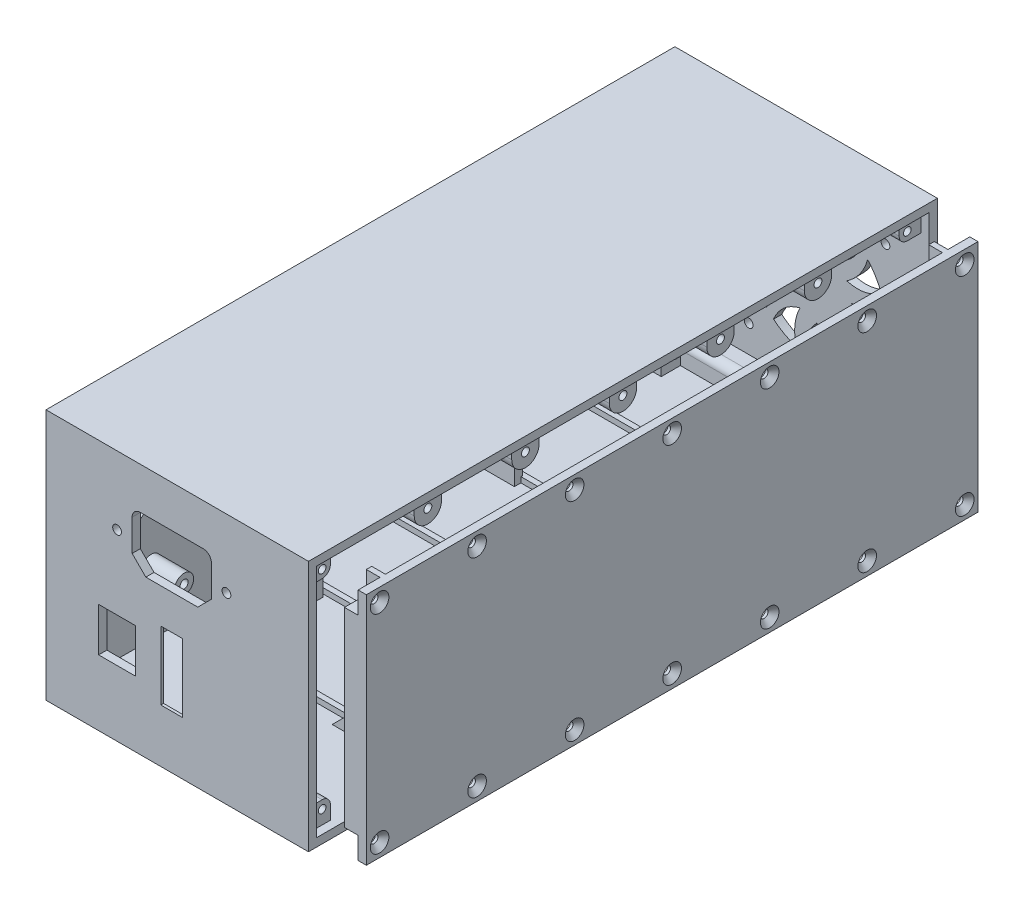
SolidWorks part; units mm, degrees
ref_plane "Front Plane" through (0, 0, 0) normal (0, 0, 1) x (1, 0, 0)
ref_plane "Top Plane" through (0, 0, 0) normal (0, 1, 0) x (1, 0, 0)
ref_plane "Right Plane" through (0, 0, 0) normal (1, 0, 0) x (0, 0, -1)
sketch "Sketch1" plane through (0, 0, 0) normal (1, 0, 0) x (0, 0, -1)
  line L1 (115, 46) -> (-115, 46)
  line L2 (115, 46) -> (115, -46)
  line L3 (115, -46) -> (-115, -46)
  line L4 (-115, 46) -> (-115, -46)
  line L5 (115, 46) -> (-115, -46) construction
  line L6 (115, -46) -> (-115, 46) construction
  point P0 (0, 0)
  dimension "D1" = 92
  dimension "D2" = 230
extrude "Boss-Extrude1" add sketch "Sketch1" along normal blind 3
sketch "Sketch2" plane through (3, 0, 0) normal (1, 0, 0) x (0, 0, -1)
  line L0 (-112, 43) -> (-112, -43)
  line L1 (-112, -43) -> (112, -43)
  line L2 (112, -43) -> (112, 43)
  line L3 (112, 43) -> (-112, 43)
  line L4 (-115, 46) -> (-115, -46)
  line L5 (-115, -46) -> (115, -46)
  line L6 (115, -46) -> (115, 46)
  line L7 (115, 46) -> (-115, 46)
  line L8 (-115, 46) -> (-115, -46)
  line L9 (-115, -46) -> (115, -46)
  line L10 (115, -46) -> (115, 46)
  line L11 (115, 46) -> (-115, 46)
  dimension "D1" = 0
  dimension "D2" = 3
extrude "Boss-Extrude2" add sketch "Sketch2" along normal blind 93
sketch "Sketch3" plane through (0, 0, 0) normal (-1, 0, 0) x (0, 0, 1)
  line L0 (-115, 0) -> (115, 0) construction
  line L1 (-115, -46) -> (-115, 46) construction
  line L2 (115, 46) -> (115, -46) construction
  line L3 (0, 46) -> (0, -46) construction
  line L4 (-115, 46) -> (115, 46) construction
  line L5 (115, -46) -> (-115, -46) construction
  line L6 (26.5, -7.75) -> (18.5, -7.75)
  line L7 (11.5, 7.75) -> (3.5, 7.75)
  line L8 (11.5, 7.75) -> (11.5, -7.75)
  line L9 (11.5, -7.75) -> (3.5, -7.75)
  line L10 (3.5, 7.75) -> (3.5, -7.75)
  line L11 (11.5, 7.75) -> (3.5, -7.75) construction
  line L12 (11.5, -7.75) -> (3.5, 7.75) construction
  line L13 (26.5, 7.75) -> (26.5, -7.75)
  line L14 (26.5, 7.75) -> (18.5, 7.75)
  line L15 (18.5, 7.75) -> (18.5, -7.75)
  line L16 (41.5, -7.75) -> (33.5, -7.75)
  line L17 (41.5, 7.75) -> (41.5, -7.75)
  line L18 (41.5, 7.75) -> (33.5, 7.75)
  line L19 (33.5, 7.75) -> (33.5, -7.75)
  line L20 (56.5, -7.75) -> (48.5, -7.75)
  line L21 (56.5, 7.75) -> (56.5, -7.75)
  line L22 (56.5, 7.75) -> (48.5, 7.75)
  line L23 (48.5, 7.75) -> (48.5, -7.75)
  line L24 (71.5, -7.75) -> (63.5, -7.75)
  line L25 (71.5, 7.75) -> (71.5, -7.75)
  line L26 (71.5, 7.75) -> (63.5, 7.75)
  line L27 (63.5, 7.75) -> (63.5, -7.75)
  line L28 (11.5, -7.75) -> (3.5, -7.75)
  line L29 (11.5, 7.75) -> (11.5, -7.75)
  line L30 (11.5, 7.75) -> (3.5, 7.75)
  line L31 (3.5, 7.75) -> (3.5, -7.75)
  line L32 (26.5, -7.75) -> (18.5, -7.75)
  line L33 (26.5, 7.75) -> (26.5, -7.75)
  line L34 (26.5, 7.75) -> (18.5, 7.75)
  line L35 (18.5, 7.75) -> (18.5, -7.75)
  line L36 (41.5, -7.75) -> (33.5, -7.75)
  line L37 (41.5, 7.75) -> (41.5, -7.75)
  line L38 (41.5, 7.75) -> (33.5, 7.75)
  line L39 (33.5, 7.75) -> (33.5, -7.75)
  line L40 (56.5, -7.75) -> (48.5, -7.75)
  line L41 (56.5, 7.75) -> (56.5, -7.75)
  line L42 (56.5, 7.75) -> (48.5, 7.75)
  line L43 (48.5, 7.75) -> (48.5, -7.75)
  line L44 (-3.5, -7.75) -> (-11.5, -7.75)
  line L45 (-3.5, 7.75) -> (-3.5, -7.75)
  line L46 (-3.5, 7.75) -> (-11.5, 7.75)
  line L47 (-11.5, 7.75) -> (-11.5, -7.75)
  line L48 (11.5, -7.75) -> (3.5, -7.75)
  line L49 (11.5, 7.75) -> (11.5, -7.75)
  line L50 (11.5, 7.75) -> (3.5, 7.75)
  line L51 (3.5, 7.75) -> (3.5, -7.75)
  line L52 (26.5, -7.75) -> (18.5, -7.75)
  line L53 (26.5, 7.75) -> (26.5, -7.75)
  line L54 (26.5, 7.75) -> (18.5, 7.75)
  line L55 (18.5, 7.75) -> (18.5, -7.75)
  line L56 (41.5, -7.75) -> (33.5, -7.75)
  line L57 (41.5, 7.75) -> (41.5, -7.75)
  line L58 (41.5, 7.75) -> (33.5, 7.75)
  line L59 (33.5, 7.75) -> (33.5, -7.75)
  line L60 (-18.5, -7.75) -> (-26.5, -7.75)
  line L61 (-18.5, 7.75) -> (-18.5, -7.75)
  line L62 (-18.5, 7.75) -> (-26.5, 7.75)
  line L63 (-26.5, 7.75) -> (-26.5, -7.75)
  line L64 (-3.5, -7.75) -> (-11.5, -7.75)
  line L65 (-3.5, 7.75) -> (-3.5, -7.75)
  line L66 (-3.5, 7.75) -> (-11.5, 7.75)
  line L67 (-11.5, 7.75) -> (-11.5, -7.75)
  line L68 (11.5, -7.75) -> (3.5, -7.75)
  line L69 (11.5, 7.75) -> (11.5, -7.75)
  line L70 (11.5, 7.75) -> (3.5, 7.75)
  line L71 (3.5, 7.75) -> (3.5, -7.75)
  line L72 (26.5, -7.75) -> (18.5, -7.75)
  line L73 (26.5, 7.75) -> (26.5, -7.75)
  line L74 (26.5, 7.75) -> (18.5, 7.75)
  line L75 (18.5, 7.75) -> (18.5, -7.75)
  line L76 (-33.5, -7.75) -> (-41.5, -7.75)
  line L77 (-33.5, 7.75) -> (-33.5, -7.75)
  line L78 (-33.5, 7.75) -> (-41.5, 7.75)
  line L79 (-41.5, 7.75) -> (-41.5, -7.75)
  line L80 (-18.5, -7.75) -> (-26.5, -7.75)
  line L81 (-18.5, 7.75) -> (-18.5, -7.75)
  line L82 (-18.5, 7.75) -> (-26.5, 7.75)
  line L83 (-26.5, 7.75) -> (-26.5, -7.75)
  line L84 (-3.5, -7.75) -> (-11.5, -7.75)
  line L85 (-3.5, 7.75) -> (-3.5, -7.75)
  line L86 (-3.5, 7.75) -> (-11.5, 7.75)
  line L87 (-11.5, 7.75) -> (-11.5, -7.75)
  line L88 (11.5, -7.75) -> (3.5, -7.75)
  line L89 (11.5, 7.75) -> (11.5, -7.75)
  line L90 (11.5, 7.75) -> (3.5, 7.75)
  line L91 (3.5, 7.75) -> (3.5, -7.75)
  line L92 (-48.5, -7.75) -> (-56.5, -7.75)
  line L93 (-48.5, 7.75) -> (-48.5, -7.75)
  line L94 (-48.5, 7.75) -> (-56.5, 7.75)
  line L95 (-56.5, 7.75) -> (-56.5, -7.75)
  line L96 (-33.5, -7.75) -> (-41.5, -7.75)
  line L97 (-33.5, 7.75) -> (-33.5, -7.75)
  line L98 (-33.5, 7.75) -> (-41.5, 7.75)
  line L99 (-41.5, 7.75) -> (-41.5, -7.75)
  line L100 (-18.5, -7.75) -> (-26.5, -7.75)
  line L101 (-18.5, 7.75) -> (-18.5, -7.75)
  line L102 (-18.5, 7.75) -> (-26.5, 7.75)
  line L103 (-26.5, 7.75) -> (-26.5, -7.75)
  line L104 (-3.5, -7.75) -> (-11.5, -7.75)
  line L105 (-3.5, 7.75) -> (-3.5, -7.75)
  line L106 (-3.5, 7.75) -> (-11.5, 7.75)
  line L107 (-11.5, 7.75) -> (-11.5, -7.75)
  line L108 (-3.5, -7.75) -> (-11.5, -7.75)
  line L109 (-3.5, 7.75) -> (-3.5, -7.75)
  line L110 (-3.5, 7.75) -> (-11.5, 7.75)
  line L111 (-11.5, 7.75) -> (-11.5, -7.75)
  line L112 (-18.5, -7.75) -> (-26.5, -7.75)
  line L113 (-18.5, 7.75) -> (-18.5, -7.75)
  line L114 (-18.5, 7.75) -> (-26.5, 7.75)
  line L115 (-26.5, 7.75) -> (-26.5, -7.75)
  line L116 (-33.5, -7.75) -> (-41.5, -7.75)
  line L117 (-33.5, 7.75) -> (-33.5, -7.75)
  line L118 (-33.5, 7.75) -> (-41.5, 7.75)
  line L119 (-41.5, 7.75) -> (-41.5, -7.75)
  line L120 (-48.5, -7.75) -> (-56.5, -7.75)
  line L121 (-48.5, 7.75) -> (-48.5, -7.75)
  line L122 (-48.5, 7.75) -> (-56.5, 7.75)
  line L123 (-56.5, 7.75) -> (-56.5, -7.75)
  line L124 (-63.5, -7.75) -> (-71.5, -7.75)
  line L125 (-63.5, 7.75) -> (-63.5, -7.75)
  line L126 (-63.5, 7.75) -> (-71.5, 7.75)
  line L127 (-71.5, 7.75) -> (-71.5, -7.75)
  circle A0 centre (84.6037, 0) radius 1
  point P12 (7.5, 0)
  dimension "D6" = 2
  dimension "D1" = 7.5
  dimension "D2" = 15.5
  dimension "D3" = 8
  dimension "D4" = 5
  dimension "D5" = 6
extrude "Cut-Extrude1" cut sketch "Sketch3" against normal up to surface (3 mm away) contours L126 L127 L124 L125 | L94 L95 L92 L93 | L78 L79 L76 L77 | L62 L63 L60 L61 | L46 L47 L44 L45 | L7 L10 L9 L8 | L14 L15 L6 L13 | L18 L19 L16 L17 | L22 L23 L20 L21 | L26 L27 L24 L25 | A0 region at (0, 0, 22.5) region at (0, 0, 7.5) region at (0, 0, 37.5) region at (0, 0, 52.5) region at (0, 0, 67.5) region at (0, 0, -7.5) region at (0, 0, -22.5) region at (0, 0, -37.5) region at (0, 0, -52.5) region at (0, 0, -67.5) region at (0, 0, 84.6037) up to face at (3, 0, 0)
sketch "Sketch4" plane through (96, 0, 0) normal (1, 0, 0) x (0, 0, -1)
  line L0 (0, 43) -> (0, -43) construction
  line L1 (112, 43) -> (-112, 43) construction
  line L2 (-112, -43) -> (112, -43) construction
  line L3 (-112, 43) -> (-112, -43) construction
  line L4 (-104, 38) -> (-104, 43)
  line L5 (-104, 43) -> (-112, 43)
  line L6 (-112, 43) -> (-112, 35)
  line L7 (-112, 35) -> (-107, 35)
  line L8 (0, 0) -> (-112, 0) construction
  line L9 (-107, -35) -> (-112, -35)
  line L10 (-112, 43) -> (-112, -43) construction
  line L11 (-112, -35) -> (-112, -43)
  line L12 (-104, -38) -> (-104, -43)
  line L13 (-104, -43) -> (-112, -43)
  line L14 (104, -43) -> (112, -43)
  line L15 (112, -35) -> (112, -43)
  line L16 (107, -35) -> (112, -35)
  line L17 (112, 35) -> (107, 35)
  line L18 (112, 43) -> (112, 35)
  line L19 (104, 43) -> (112, 43)
  line L20 (104, 38) -> (104, 43)
  line L21 (104, -38) -> (104, -43)
  circle A0 centre (-107, 38) radius 1.4
  circle A1 centre (-107, -38) radius 1.4
  arc A2 (-104, 38) -> (-107, 35) centre (-107, 38) cw
  arc A3 (-107, -35) -> (-104, -38) centre (-107, -38) cw
  arc A4 (107, -35) -> (104, -38) centre (107, -38) ccw
  circle A5 centre (107, -38) radius 1.4
  arc A6 (104, 38) -> (107, 35) centre (107, 38) ccw
  circle A7 centre (107, 38) radius 1.4
  dimension "D5" = 2.8
  dimension "D6" = 3
  dimension "D1" = 5
  dimension "D2" = 5
  dimension "D3" = 5
  dimension "D4" = 5
extrude "Boss-Extrude3" add sketch "Sketch4" against normal up to surface (93 mm away) from offset 3 up to face at (3, 0, -67.5) offset against normal yes
sketch "Sketch5" plane through (93, 0, 0) normal (1, 0, 0) x (0, 0, -1)
  circle A0 centre (-107, -38) radius 1.4 construction
  circle A1 centre (107, -38) radius 1.4 construction
  circle A2 centre (107, 38) radius 1.4 construction
  circle A3 centre (-107, 38) radius 1.4 construction
  circle A4 centre (-107, -38) radius 1.4
  circle A5 centre (107, -38) radius 1.4
  circle A6 centre (107, 38) radius 1.4
  circle A7 centre (-107, 38) radius 1.4
extrude "Boss-Extrude4" add sketch "Sketch5" against normal up to surface (90 mm away) from offset 20 up to face at (3, 0, -67.5) offset against normal yes
sketch "Sketch6" plane through (0, 0, 115) normal (0, 0, 1) x (1, 0, 0)
  line L0 (46, 46) -> (46, -46) construction
  line L1 (96, 46) -> (0, 46) construction
  line L2 (96, -46) -> (0, -46) construction
  line L3 (93, 43) -> (93, 38) construction
  line L4 (79.2275, 21) -> (12.7725, 21) construction
  line L5 (36.5, 11.25) -> (31.5, 16.25)
  line L6 (57.5, 30.75) -> (34.5, 30.75)
  line L7 (60.5, 27.75) -> (60.5, 16.25)
  line L8 (55.5, 11.25) -> (36.5, 11.25)
  line L9 (31.5, 27.75) -> (31.5, 16.25)
  line L10 (60.5, 30.75) -> (31.5, 11.25) construction
  line L11 (60.5, 11.25) -> (31.5, 30.75) construction
  line L12 (60.5, 16.25) -> (55.5, 11.25)
  line L14 (50, -1.5) -> (42, -1.5)
  line L15 (50, -1.5) -> (50, -26.5)
  line L16 (50, -26.5) -> (42, -26.5)
  line L17 (42, -1.5) -> (42, -26.5)
  line L18 (50, -1.5) -> (42, -26.5) construction
  line L19 (50, -26.5) -> (42, -1.5) construction
  line L20 (32.75, -6) -> (19.25, -6)
  line L21 (32.75, -6) -> (32.75, -22)
  line L22 (32.75, -22) -> (19.25, -22)
  line L23 (19.25, -6) -> (19.25, -22)
  line L24 (32.75, -6) -> (19.25, -22) construction
  line L25 (32.75, -22) -> (19.25, -6) construction
  circle A2 centre (26, 21) radius 1.6
  circle A3 centre (66, 21) radius 1.6
  arc A4 (57.5, 30.75) -> (60.5, 27.75) centre (57.5, 27.75) cw
  arc A5 (34.5, 30.75) -> (31.5, 27.75) centre (34.5, 27.75) ccw
  point P11 (46, 21)
  point P15 (46, 21)
  point P30 (46, -14)
  point P35 (26, -14)
  dimension "D2" = 3.2
  dimension "D7" = 3
  dimension "D1" = 47
  dimension "D3" = 20
  dimension "D4" = 20
  dimension "D5" = 29
  dimension "D6" = 19.5
  dimension "D8" = 25
  dimension "D9" = 8
  dimension "D10" = 25
  dimension "D13" = 32
  dimension "D14" = 20
  dimension "D15" = 13.5
  dimension "D16" = 16
extrude "Cut-Extrude2" cut sketch "Sketch6" against normal up to surface (3 mm away) up to face at (71.25, 0, 112)
sketch "Sketch7" plane through (0, 0, 112) normal (0, 0, -1) x (-1, 0, 0)
  line L0 (-39.5, 6) -> (-39.5, -32.5)
  line L1 (-39.5, -32.5) -> (-52, -32.5)
  line L2 (-52, -32.5) -> (-52, 6)
  line L3 (-52, 6) -> (-39.5, 6)
  line L4 (-50, -1.5) -> (-42, -1.5) construction
  line L5 (-50, -26.5) -> (-50, -1.5) construction
  dimension "D1" = 7.5
  dimension "D2" = 2
  dimension "D3" = 38.5
  dimension "D4" = 12.5
extrude "Cut-Extrude3" cut sketch "Sketch7" against normal blind 2
chamfer "Chamfer1" distance 2 angle 45 1 edges at (52, -13.25, 112)
sketch "Sketch8" plane through (3, 0, 0) normal (1, 0, 0) x (0, 0, -1)
  line L0 (-71.5, 0) -> (91.1958, 0) construction
  line L1 (-71.5, -7.75) -> (-71.5, 7.75) construction
  line L2 (-79.5, 43) -> (-79.5, -43) construction
  line L3 (112, 43) -> (-112, 43) construction
  line L4 (-104, -43) -> (104, -43) construction
  circle A0 centre (-79.5, 19.5) radius 1.5
  circle A1 centre (-79.5, -19.5) radius 1.5
  circle A2 centre (-79.5, 19.5) radius 3.5
  circle A3 centre (-79.5, -19.5) radius 3.5
  circle A4 centre (72, -19.5) radius 1.5
  circle A5 centre (72, -19.5) radius 3.5
  circle A6 centre (72, 19.5) radius 3.5
  circle A7 centre (72, 19.5) radius 1.5
  dimension "D1" = 3
  dimension "D2" = 7
  dimension "D3" = 8
  dimension "D5" = 19.5
  dimension "D6" = 19.5
  dimension "D7" = 19.5
  dimension "D8" = 19.5
  dimension "D9" = 151.5
extrude "Boss-Extrude5" add sketch "Sketch8" along normal blind 12
sketch "Sketch9" plane through (3, 0, 0) normal (1, 0, 0) x (0, 0, -1)
  circle A0 centre (-84.6037, 0) radius 3
extrude "Cut-Extrude4" cut sketch "Sketch9" against normal blind 2.2
ref_plane "Plane1" through (106, 0, 0) normal (1, 0, 0) x (0, 0, -1)
sketch "Sketch10" plane through (106, 0, 0) normal (1, 0, 0) x (0, 0, -1)
  line L112 (107, -32.85) -> (109.85, -32.85)
  line L113 (109.85, -32.85) -> (109.85, 32.85)
  line L114 (109.85, 32.85) -> (107, 32.85)
  line L115 (101.85, 38) -> (101.85, 40.85)
  line L116 (101.85, 40.85) -> (-101.85, 40.85)
  line L117 (-101.85, 40.85) -> (-101.85, 38)
  line L118 (-107, 32.85) -> (-109.85, 32.85)
  line L119 (-109.85, 32.85) -> (-109.85, -32.85)
  line L120 (-109.85, -32.85) -> (-107, -32.85)
  line L121 (-101.85, -38) -> (-101.85, -40.85)
  line L122 (-101.85, -40.85) -> (101.85, -40.85)
  line L123 (101.85, -40.85) -> (101.85, -38)
  line L124 (107, -34.85) -> (111.85, -34.85)
  line L125 (103.85, -42.85) -> (103.85, -38)
  line L126 (-103.85, -42.85) -> (103.85, -42.85)
  line L127 (-103.85, -38) -> (-103.85, -42.85)
  line L128 (-111.85, -34.85) -> (-107, -34.85)
  line L129 (-111.85, 34.85) -> (-111.85, -34.85)
  line L130 (-107, 34.85) -> (-111.85, 34.85)
  line L131 (-103.85, 42.85) -> (-103.85, 38)
  line L132 (103.85, 42.85) -> (-103.85, 42.85)
  line L133 (103.85, 38) -> (103.85, 42.85)
  line L134 (111.85, 34.85) -> (107, 34.85)
  line L135 (111.85, -34.85) -> (111.85, 34.85)
  line L136 (107, -34.85) -> (111.85, -34.85)
  line L137 (103.85, -42.85) -> (103.85, -38)
  line L138 (-103.85, -42.85) -> (103.85, -42.85)
  line L139 (-103.85, -38) -> (-103.85, -42.85)
  line L140 (-111.85, -34.85) -> (-107, -34.85)
  line L141 (-111.85, 34.85) -> (-111.85, -34.85)
  line L142 (-107, 34.85) -> (-111.85, 34.85)
  line L143 (-103.85, 42.85) -> (-103.85, 38)
  line L144 (103.85, 42.85) -> (-103.85, 42.85)
  line L145 (103.85, 38) -> (103.85, 42.85)
  line L146 (111.85, 34.85) -> (107, 34.85)
  line L147 (111.85, -34.85) -> (111.85, 34.85)
  arc A36 (107, -34.85) -> (103.85, -38) centre (107, -38) ccw
  arc A37 (-103.85, -38) -> (-107, -34.85) centre (-107, -38) ccw
  arc A38 (-107, 34.85) -> (-103.85, 38) centre (-107, 38) ccw
  arc A39 (103.85, 38) -> (107, 34.85) centre (107, 38) ccw
  arc A40 (107, -34.85) -> (103.85, -38) centre (107, -38) ccw
  arc A41 (-103.85, -38) -> (-107, -34.85) centre (-107, -38) ccw
  arc A42 (-107, 34.85) -> (-103.85, 38) centre (-107, 38) ccw
  arc A43 (103.85, 38) -> (107, 34.85) centre (107, 38) ccw
  arc A48 (101.85, 38) -> (107, 32.85) centre (107, 38) ccw
  arc A49 (-107, 32.85) -> (-101.85, 38) centre (-107, 38) ccw
  arc A50 (-101.85, -38) -> (-107, -32.85) centre (-107, -38) ccw
  arc A51 (107, -32.85) -> (101.85, -38) centre (107, -38) ccw
  dimension "D1" = 0.15
  dimension "D2" = 2
extrude "Boss-Extrude6" add sketch "Sketch10" along normal blind 5 separate body
sketch "Sketch11" plane through (111, 0, 0) normal (1, 0, 0) x (0, 0, -1)
  line L0 (111.85, -34.85) -> (111.85, 34.85) construction
  line L1 (-103.85, -42.85) -> (103.85, -42.85) construction
  line L2 (-111.85, 34.85) -> (-111.85, -34.85) construction
  line L3 (103.85, 42.85) -> (-103.85, 42.85) construction
  line L4 (111.85, -34.85) -> (111.85, 34.85)
  line L5 (-103.85, -42.85) -> (103.85, -42.85)
  line L6 (-111.85, 34.85) -> (-111.85, -34.85)
  line L7 (103.85, 42.85) -> (-103.85, 42.85)
  line L8 (103.85, 42.85) -> (111.85, 42.85)
  line L9 (111.85, 42.85) -> (111.85, 34.85)
  line L10 (111.85, -34.85) -> (111.85, -42.85)
  line L11 (111.85, -42.85) -> (103.85, -42.85)
  line L12 (-111.85, -34.85) -> (-111.85, -42.85)
  line L13 (-111.85, -42.85) -> (-103.85, -42.85)
  line L14 (-103.85, 42.85) -> (-111.85, 42.85)
  line L15 (-111.85, 42.85) -> (-111.85, 34.85)
  circle A0 centre (-107, -38) radius 1.4 construction
  circle A1 centre (107, -38) radius 1.4 construction
  circle A2 centre (107, 38) radius 1.4 construction
  circle A3 centre (-107, 38) radius 1.4 construction
  circle A4 centre (-107, -38) radius 1.4
  circle A5 centre (107, -38) radius 1.4
  circle A6 centre (107, 38) radius 1.4
  circle A7 centre (-107, 38) radius 1.4
extrude "Boss-Extrude7" add sketch "Sketch11" along normal blind 3
sketch "Sketch12" plane through (114, 0, 0) normal (1, 0, 0) x (0, 0, -1)
  line L0 (-112, 0) -> (111.85, 0) construction
  line L1 (89, 29.25) -> (-89, 29.25) construction
  line L2 (89, 29.25) -> (89, -29.25) construction
  line L3 (89, -29.25) -> (-89, -29.25) construction
  line L4 (-89, 29.25) -> (-89, -29.25) construction
  line L5 (89, 29.25) -> (-89, -29.25) construction
  line L6 (89, -29.25) -> (-89, 29.25) construction
  line L7 (-112, 43) -> (-112, -43) construction
  line L8 (111.85, -42.85) -> (111.85, 42.85) construction
  circle A0 centre (-89, 29.25) radius 1.8
  circle A1 centre (-89, -29.25) radius 1.8
  circle A2 centre (89, -29.25) radius 1.8
  circle A3 centre (89, 29.25) radius 1.8
  circle A4 centre (-47.3819, 9) radius 1.8
  circle A5 centre (26.6181, 9) radius 1.8
  circle A6 centre (-4.3819, 9) radius 1.8
  circle A7 centre (-4.3819, -9) radius 1.8
  point P0 (0, 0)
  dimension "D3" = 3.6
  dimension "D10" = 3.6
  dimension "D1" = 58.5
  dimension "D2" = 178
  dimension "D4" = 9
  dimension "D5" = 9
  dimension "D6" = 74
  dimension "D7" = 31
  dimension "D8" = 9
  dimension "D9" = 9
sketch "Sketch13" plane through (96, 0, 0) normal (1, 0, 0) x (0, 0, -1)
  line L12 (104, 38) -> (104, 43)
  line L13 (104, 43) -> (-104, 43)
  line L14 (-104, 43) -> (-104, 38)
  line L15 (-107, 35) -> (-112, 35)
  line L16 (-112, 35) -> (-112, -35)
  line L17 (-112, -35) -> (-107, -35)
  line L18 (-104, -38) -> (-104, -43)
  line L19 (-104, -43) -> (104, -43)
  line L20 (104, -43) -> (104, -38)
  line L21 (107, -35) -> (112, -35)
  line L22 (112, -35) -> (112, 35)
  line L23 (112, 35) -> (107, 35)
  line L24 (104, 38) -> (104, 43)
  line L25 (104, 43) -> (-104, 43)
  line L26 (-104, 43) -> (-104, 38)
  line L27 (-107, 35) -> (-112, 35)
  line L28 (-112, 35) -> (-112, -35)
  line L29 (-112, -35) -> (-107, -35)
  line L30 (-104, -38) -> (-104, -43)
  line L31 (-104, -43) -> (104, -43)
  line L32 (104, -43) -> (104, -38)
  line L33 (107, -35) -> (112, -35)
  line L34 (112, -35) -> (112, 35)
  line L35 (112, 35) -> (107, 35)
  arc A4 (104, 38) -> (107, 35) centre (107, 38) ccw
  arc A5 (-107, 35) -> (-104, 38) centre (-107, 38) ccw
  arc A6 (-104, -38) -> (-107, -35) centre (-107, -38) ccw
  arc A7 (107, -35) -> (104, -38) centre (107, -38) ccw
  arc A8 (104, 38) -> (107, 35) centre (107, 38) ccw
  arc A9 (-107, 35) -> (-104, 38) centre (-107, 38) ccw
  arc A10 (-104, -38) -> (-107, -35) centre (-107, -38) ccw
  arc A11 (107, -35) -> (104, -38) centre (107, -38) ccw
  dimension "D1" = 0
sketch "Sketch14" plane through (93, 0, 0) normal (1, 0, 0) x (0, 0, -1)
  line L0 (-68.334, -43) -> (-68.334, -41)
  line L2 (-104, -43) -> (-104, -38) construction
  line L3 (-68.334, 43) -> (-68.334, 41)
  line L5 (-104, 38) -> (-104, 43) construction
  dimension "D1" = 35.666
  dimension "D2" = 35.666
extrude "Extrude-Thin2" add sketch "Sketch14" against normal up to surface (90 mm away) from offset 3 thin up to face at (3, 0, 81.6037) offset against normal yes thin type mid plane wall 2
pattern_linear "LPattern1" count 5 spacing 35.666 along (0, 0, -1) of "Extrude-Thin2"
sketch "Sketch15" plane through (3, 40, 0) normal (1, 0, 0) x (0, 1, 0)
  line L0 (-40, 112) -> (-40, -112.6115) construction
  line L2 (-5, 112) -> (-75, 112) construction
  line L3 (-13.5, 36.1943) -> (-66.5, 36.1943) construction
  line L4 (-13.5, 36.1943) -> (-13.5, -36.8057) construction
  line L5 (-13.5, -36.8057) -> (-66.5, -36.8057) construction
  line L6 (-66.5, 36.1943) -> (-66.5, -36.8057) construction
  line L7 (-13.5, 36.1943) -> (-66.5, -36.8057) construction
  line L8 (-13.5, -36.8057) -> (-66.5, 36.1943) construction
  circle A0 centre (-13.5, 36.1943) radius 1.25
  circle A1 centre (-66.5, 36.1943) radius 1.25
  circle A2 centre (-66.5, -36.8057) radius 1.25
  circle A4 centre (-66.5, 36.1943) radius 2.5
  circle A5 centre (-13.5, 36.1943) radius 2.5
  circle A7 centre (-66.5, -36.8057) radius 2.5
  circle A8 centre (-13.5, -36.8057) radius 1.25
  circle A9 centre (-13.5, -36.8057) radius 2.5
  point P4 (-40, -0.3057)
  point P20 (-40, 112)
  dimension "D3" = 2.5
  dimension "D4" = 5
  dimension "D1" = 53
  dimension "D2" = 73
extrude "Boss-Extrude9" add sketch "Sketch15" along normal blind 20
sketch "Sketch16" plane through (0, 0, -112) normal (0, 0, 1) x (1, 0, 0)
  line L0 (3, 0) -> (96, 0) construction
  line L1 (3, -35) -> (3, 35) construction
  line L3 (55, 0) -> (67.5, 0) construction
  line L4 (80, 25) -> (30, 25) construction
  line L5 (80, 25) -> (80, -25) construction
  line L6 (80, -25) -> (30, -25) construction
  line L7 (30, 25) -> (30, -25) construction
  line L8 (80, 25) -> (30, -25) construction
  line L9 (80, -25) -> (30, 25) construction
  line L10 (55, 0) -> (65.8253, -6.25) construction
  line L11 (96, -35) -> (96, 35) construction
  circle A0 centre (30, 25) radius 1.6
  circle A1 centre (80, 25) radius 1.6
  circle A2 centre (80, -25) radius 1.6
  circle A3 centre (30, -25) radius 1.6
  circle A4 centre (55, 0) radius 12.5 construction
  arc A5 (79.4256, 5.3285) -> (79.6515, -4.1595) centre (55, 0) cw
  arc A6 (78.8174, -7.5982) -> (74.2691, -15.928) centre (55, 0) cw
  arc A7 (71.8274, -18.4889) -> (63.7236, -23.4286) centre (55, 0) cw
  arc A8 (60.3285, -24.4256) -> (50.8405, -24.6515) centre (55, 0) cw
  arc A9 (47.4018, -23.8174) -> (39.072, -19.2691) centre (55, 0) cw
  arc A10 (36.5111, -16.8274) -> (31.5714, -8.7236) centre (55, 0) cw
  arc A11 (30.5744, -5.3285) -> (30.3485, 4.1595) centre (55, 0) cw
  arc A12 (31.1826, 7.5982) -> (35.7309, 15.928) centre (55, 0) cw
  arc A13 (38.1726, 18.4889) -> (46.2764, 23.4286) centre (55, 0) cw
  arc A14 (49.6715, 24.4256) -> (59.1595, 24.6515) centre (55, 0) cw
  arc A15 (62.5982, 23.8174) -> (70.928, 19.2691) centre (55, 0) cw
  arc A16 (73.4889, 16.8274) -> (78.4286, 8.7236) centre (55, 0) cw
  spline S0 degree 2 poles (79.4256, 5.3285) (74.5238, 0.5174) (67.5, 0) knots 0 0 0 1 1 1
  spline S1 degree 2 poles (67.5, 0) (72.6575, -5.0815) (79.6515, -4.1595) knots 0 0 0 1 1 1
  spline S2 degree 2 poles (78.8174, -7.5982) (72.1668, -9.3138) (65.8253, -6.25) knots 0 0 0 1 1 1
  spline S3 degree 2 poles (65.8253, -6.25) (67.7511, -13.2294) (74.2691, -15.928) knots 0 0 0 1 1 1
  spline S4 degree 2 poles (71.8274, -18.4889) (65.21, -16.6494) (61.25, -10.8253) knots 0 0 0 1 1 1
  spline S5 degree 2 poles (61.25, -10.8253) (59.428, -17.8326) (63.7236, -23.4286) knots 0 0 0 1 1 1
  spline S6 degree 2 poles (60.3285, -24.4256) (55.5174, -19.5238) (55, -12.5) knots 0 0 0 1 1 1
  spline S7 degree 2 poles (55, -12.5) (49.9185, -17.6575) (50.8405, -24.6515) knots 0 0 0 1 1 1
  spline S8 degree 2 poles (47.4018, -23.8174) (45.6862, -17.1668) (48.75, -10.8253) knots 0 0 0 1 1 1
  spline S9 degree 2 poles (48.75, -10.8253) (41.7706, -12.7511) (39.072, -19.2691) knots 0 0 0 1 1 1
  spline S10 degree 2 poles (36.5111, -16.8274) (38.3506, -10.21) (44.1747, -6.25) knots 0 0 0 1 1 1
  spline S11 degree 2 poles (44.1747, -6.25) (37.1674, -4.428) (31.5714, -8.7236) knots 0 0 0 1 1 1
  spline S12 degree 2 poles (30.5744, -5.3285) (35.4762, -0.5174) (42.5, 0) knots 0 0 0 1 1 1
  spline S13 degree 2 poles (42.5, 0) (37.3425, 5.0815) (30.3485, 4.1595) knots 0 0 0 1 1 1
  spline S14 degree 2 poles (31.1826, 7.5982) (37.8332, 9.3138) (44.1747, 6.25) knots 0 0 0 1 1 1
  spline S15 degree 2 poles (44.1747, 6.25) (42.2489, 13.2294) (35.7309, 15.928) knots 0 0 0 1 1 1
  spline S16 degree 2 poles (38.1726, 18.4889) (44.79, 16.6494) (48.75, 10.8253) knots 0 0 0 1 1 1
  spline S17 degree 2 poles (48.75, 10.8253) (50.572, 17.8326) (46.2764, 23.4286) knots 0 0 0 1 1 1
  spline S18 degree 2 poles (49.6715, 24.4256) (54.4826, 19.5238) (55, 12.5) knots 0 0 0 1 1 1
  spline S19 degree 2 poles (55, 12.5) (60.0815, 17.6575) (59.1595, 24.6515) knots 0 0 0 1 1 1
  spline S20 degree 2 poles (62.5982, 23.8174) (64.3138, 17.1668) (61.25, 10.8253) knots 0 0 0 1 1 1
  spline S21 degree 2 poles (61.25, 10.8253) (68.2294, 12.7511) (70.928, 19.2691) knots 0 0 0 1 1 1
  spline S22 degree 2 poles (73.4889, 16.8274) (71.6494, 10.21) (65.8253, 6.25) knots 0 0 0 1 1 1
  spline S23 degree 2 poles (65.8253, 6.25) (72.8326, 4.428) (78.4286, 8.7236) knots 0 0 0 1 1 1
  point P6 (55, 0)
  point P83 (96, 0)
  dimension "D4" = 3.2
  dimension "D5" = 25
  dimension "D6" = 12
  dimension "D1" = 50
  dimension "D2" = 50
  dimension "D7" = 30
extrude "Cut-Extrude6" cut sketch "Sketch16" against normal up to surface (3 mm away) up to face at (48, 0, -115)
sketch "Sketch17" plane through (111, 0, 0) normal (-1, 0, 0) x (0, 0, 1)
  line L0 (-109.85, -0.85) -> (109.85, -0.85) construction
  line L1 (-109.85, -32.85) -> (-109.85, 32.85) construction
  line L2 (109.85, 32.85) -> (109.85, -32.85) construction
  line L3 (101.85, -40.85) -> (-101.85, -40.85) construction
  line L4 (-8.5, 20.1) -> (-91.2, 20.1) construction
  line L5 (-8.5, 20.1) -> (-8.5, -21.8) construction
  line L6 (-8.5, -21.8) -> (-91.2, -21.8) construction
  line L7 (-91.2, 20.1) -> (-91.2, -21.8) construction
  line L8 (-8.5, 20.1) -> (-91.2, -21.8) construction
  line L9 (-8.5, -21.8) -> (-91.2, 20.1) construction
  line L10 (79.15, 12.15) -> (21.15, 12.15) construction
  line L11 (79.15, 12.15) -> (79.15, -13.85) construction
  line L12 (79.15, -13.85) -> (21.15, -13.85) construction
  line L13 (21.15, 12.15) -> (21.15, -13.85) construction
  line L14 (79.15, 12.15) -> (21.15, -13.85) construction
  line L15 (79.15, -13.85) -> (21.15, 12.15) construction
  line L16 (-109.85, -32.85) -> (-109.85, 32.85) construction
  circle A0 centre (-91.2, 20.1) radius 1.4
  circle A1 centre (-91.2, -21.8) radius 1.4
  circle A2 centre (-8.5, -21.8) radius 1.4
  circle A3 centre (-8.5, 20.1) radius 1.4
  circle A4 centre (79.15, 12.15) radius 1.4
  circle A5 centre (21.15, 12.15) radius 1.4
  circle A6 centre (21.15, -13.85) radius 1.4
  circle A7 centre (79.15, -13.85) radius 1.4
  circle A8 centre (-91.2, 20.1) radius 3.25
  circle A9 centre (-8.5, 20.1) radius 3.25
  circle A10 centre (-8.5, -21.8) radius 3.25
  circle A11 centre (-91.2, -21.8) radius 3.25
  circle A12 centre (21.15, -13.85) radius 3.25
  circle A13 centre (21.15, 12.15) radius 3.25
  circle A14 centre (79.15, 12.15) radius 3.25
  circle A15 centre (79.15, -13.85) radius 3.25
  point P6 (-49.85, -0.85)
  point P11 (50.15, -0.85)
  dimension "D8" = 2.8
  dimension "D9" = 6.5
  dimension "D1" = 82.7
  dimension "D2" = 41.9
  dimension "D3" = 40
  dimension "D4" = 60
  dimension "D5" = 58
  dimension "D6" = 26
  dimension "D7" = 100
extrude "Boss-Extrude10" add sketch "Sketch17" along normal blind 5
sketch "Sketch18" plane through (93, 0, 0) normal (1, 0, 0) x (0, 0, -1)
  line L0 (74.33, -41) -> (74.33, -35.3123) construction
  line L1 (73.33, -41) -> (75.33, -41) construction
  line L2 (-112, -43) -> (112, -43) construction
  line L3 (69.33, -38) -> (69.33, -43)
  line L5 (69.33, -43) -> (79.33, -43)
  line L6 (79.33, -43) -> (79.33, -38)
  circle A0 centre (74.33, -38) radius 1.45
  arc A1 (69.33, -38) -> (79.33, -38) centre (74.33, -38) cw
  dimension "D1" = 2.9
  dimension "D3" = 5
  dimension "D2" = 5
extrude "Boss-Extrude11" add sketch "Sketch18" against normal blind 20
chamfer "Chamfer3" distance 10 angle 45 1 edges at (73, -43, -71.33)
ref_plane "Plane2" through (0, 0, 0) normal (0, -1, 0) x (-1, 0, 0)
mirror "Mirror4" about plane through (0, 0, 0) normal (0, -1, 0) of "Boss-Extrude11"
chamfer "Chamfer4" distance 10 angle 45 1 edges at (73, 43, -71.33)
pattern_linear "LPattern4" count 5 spacing 35.666 along (0, 0, 1) of "Boss-Extrude11", "Chamfer3", "Mirror4", "Chamfer4"
sketch "Sketch21" plane through (106, 0, 0) normal (-1, 0, 0) x (0, 0, 1)
  line L0 (-101.85, -44.15) -> (-101.85, -36.4687)
  line L1 (-101.85, 40.85) -> (101.8627, 40.85)
  line L2 (-101.85, 40.85) -> (-101.85, 48.5313)
  line L3 (-101.85, 48.5313) -> (101.8627, 48.5313)
  line L4 (101.8627, 40.85) -> (101.8627, 48.5313)
  line L5 (-101.85, -44.15) -> (101.8627, -44.15)
  line L6 (101.8627, -44.15) -> (101.8627, -36.4687)
  line L7 (-101.85, -36.4687) -> (101.8627, -36.4687)
  dimension "D1" = 2
extrude "Cut-Extrude7" cut sketch "Sketch21" against normal up to surface (5 mm away) up to face at (111, -13.85, 82.4)
sketch "Sketch22" plane through (114, 0, 0) normal (1, 0, 0) x (0, 0, -1)
  line L0 (-107, 38) -> (-71.334, 38) construction
  line L1 (-111.85, 0) -> (111.85, 0) construction
  line L2 (-111.85, 42.85) -> (-111.85, -42.85) construction
  line L3 (111.85, -42.85) -> (111.85, 42.85) construction
  circle A0 centre (-71.334, 38) radius 1.4
  circle A1 centre (-107, 38) radius 1.4 construction
  circle A2 centre (-35.668, 38) radius 1.4
  circle A3 centre (-0.002, 38) radius 1.4
  circle A4 centre (35.664, 38) radius 1.4
  circle A5 centre (71.33, 38) radius 1.4
  circle A6 centre (71.33, -38) radius 1.4
  circle A7 centre (35.664, -38) radius 1.4
  circle A8 centre (-0.002, -38) radius 1.4
  circle A9 centre (-35.668, -38) radius 1.4
  circle A10 centre (-71.334, -38) radius 1.4
  dimension "D2" = 35.666
  dimension "D3" = 35.666
  dimension "D1" = 5
extrude "Cut-Extrude8" cut sketch "Sketch22" against normal up to surface (3 mm away) up to face at (111, 4.5559, 11.3264)
chamfer "Chamfer5" distance 2 angle 45 14 edges at (114, -38, 105.6) (114, -38, 72.734) (114, -38, 37.068) (114, -38, 1.402) (114, -38, -34.264) (114, -38, -69.93) (114, -38, -108.4) (114, 38, -37.064) (114, 38, -1.398) (114, 38, 34.268) (114, 38, 105.6) (114, 38, 69.934) (114, 38, -108.4) (114, 38, -72.73)
sketch "Sketch23" plane through (0, 0, -112) normal (0, 0, 1) x (1, 0, 0)
  line L0 (3, 0) -> (96, 0) construction
  line L1 (3, -35) -> (3, 35) construction
  line L2 (96, -43) -> (96, 43) construction
  line L3 (3, 30.1015) -> (3, 43)
  line L4 (3, 43) -> (93, 43) construction
  line L6 (3, 43) -> (13, 43)
  line L7 (13, 43) -> (13, 33)
  line L8 (13, 33) -> (3, 30.1015)
  line L9 (13, -33) -> (3, -30.1015)
  line L10 (13, -43) -> (13, -33)
  line L11 (3, -43) -> (13, -43)
  line L12 (3, -30.1015) -> (3, -43)
  circle A0 centre (8, 35.5) radius 1.6
  circle A1 centre (8, -35.5) radius 1.6
  dimension "D1" = 3.2
  dimension "D2" = 5
  dimension "D3" = 71
  dimension "D4" = 10
  dimension "D5" = 10
extrude "Boss-Extrude12" add sketch "Sketch23" along normal blind 15
sketch "Sketch24" plane through (0, 0, 0) normal (-1, 0, 0) x (0, 0, 1)
  line L0 (-115, 0) -> (-89.7581, 0) construction
  line L1 (-115, -46) -> (-115, 46) construction
  line L3 (-101.8, 40.1) -> (-112, 40.1)
  line L4 (-101.8, 40.1) -> (-101.8, -40.1)
  line L5 (-101.8, -40.1) -> (-112, -40.1)
  line L6 (-112, 40.1) -> (-112, -40.1)
  line L7 (-101.8, 40.1) -> (-112, -40.1) construction
  line L8 (-101.8, -40.1) -> (-112, 40.1) construction
  point P5 (-106.9, 0)
  dimension "D1" = 3
  dimension "D2" = 10.2
  dimension "D3" = 80.2
extrude "Cut-Extrude9" cut sketch "Sketch24" against normal up to surface (13 mm away) up to face at (13, 37.0541, -104.6255)
sketch "Sketch25" plane through (0, 0, -115) normal (0, 0, -1) x (-1, 0, 0)
  circle A0 centre (-8, 35.5) radius 1.6
  circle A1 centre (-8, -35.5) radius 1.6
  dimension "D1" = 3.2
extrude "Cut-Extrude10" cut sketch "Sketch25" against normal up to surface (3 mm away) up to face at (51.3333, 0, -112)
sketch "Sketch26" plane through (23, 0, 0) normal (1, 0, 0) x (0, 0, -1)
  line L1 (53.3288, 25) -> (-53.3288, 25)
  line L2 (53.3288, 25) -> (53.3288, -25)
  line L3 (53.3288, -25) -> (-53.3288, -25)
  line L4 (-53.3288, 25) -> (-53.3288, -25)
  line L5 (53.3288, 25) -> (-53.3288, -25) construction
  line L6 (53.3288, -25) -> (-53.3288, 25) construction
  point P0 (0, 0)
  dimension "D1" = 50
extrude "Cut-Extrude11" cut sketch "Sketch26" against normal up to surface (8 mm away) up to face at (15, 19.5, 76)
ref_plane "Plane3" through (0, 0, 36.1943) normal (0, 0, 1) x (1, 0, 0)
sketch "Sketch27" plane through (0, 0, 36.1943) normal (0, 0, 1) x (1, 0, 0)
  line L0 (21, -29) -> (21, -43)
  line L1 (3, 24) -> (3, 29) construction
  line L2 (3, -43) -> (13, -43) construction
  line L3 (3, -29) -> (3, -24) construction
  point P3 (0, 0)
  point P6 (0, 0)
  point P11 (0, 0)
  dimension "D1" = 18
rib "Rib12" sketch "Sketch27" sketch "Sketch27" thickness 3 extrusion direction parallel to sketch draft on no parameters "D1"=3
pattern_linear "LPattern5" count 2 spacing 73 along (0, 0, -1) of "Rib12"
mirror "Mirror5" about plane through (0, 0, 0) normal (0, -1, 0) of "LPattern5", "Rib12"
